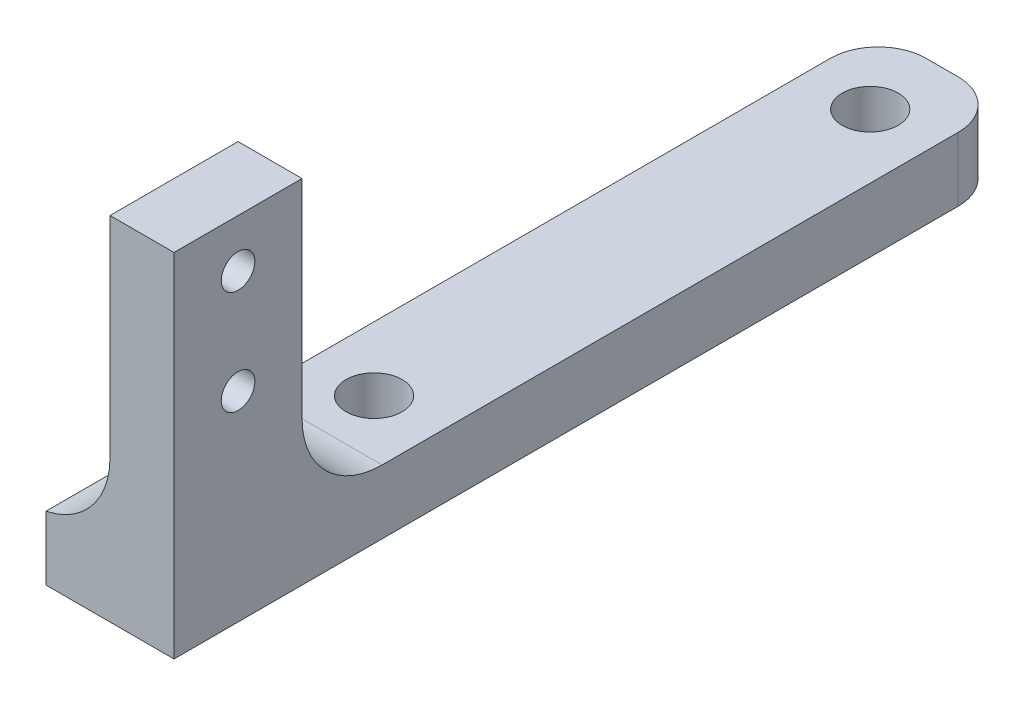
SolidWorks part; units mm, degrees
ref_plane "Front Plane" through (0, 0, 0) normal (0, 0, 1) x (1, 0, 0)
ref_plane "Top Plane" through (0, 0, 0) normal (0, 1, 0) x (1, 0, 0)
ref_plane "Right Plane" through (0, 0, 0) normal (1, 0, 0) x (0, 0, -1)
sketch "Sketch1" plane through (0, 0, 0) normal (0, 1, 0) x (1, 0, 0)
  line L2 (0, 0) -> (0, 31)
  line L3 (4, -16.5) -> (0, -16.5)
  line L10 (4, -4) -> (0, -4)
  line L11 (4, -4) -> (4, -16.5)
  line L12 (4, -16.5) -> (0, -16.5)
  line L13 (0, -4) -> (0, -16.5)
  line L14 (4, -16.5) -> (4, -8.5)
  line L15 (4, -8.5) -> (0, -8.5)
  line L16 (0, -16.5) -> (0, -8.5)
  line L17 (4, -16.5) -> (-4, -16.5)
  line L18 (4, -16.5) -> (4, 35.5)
  line L19 (4, 35.5) -> (-4, 35.5)
  line L20 (-4, -16.5) -> (-4, 35.5)
  circle A0 centre (0, 0) radius 1.75
  circle A2 centre (0, 31) radius 1.75
  dimension "D2" = 3.5
  dimension "D10" = 3.5
  dimension "D3" = 8
  dimension "D4" = 0
  dimension "D5" = 4
  dimension "D6" = 4
  dimension "D7" = 12.5
  dimension "D8" = 31
  dimension "D9" = 52
  dimension "D11" = 8
  dimension "D12" = 16.5
extrude "Boss-Extrude1" add sketch "Sketch1" along normal blind 4 contours A0 | L15 L11 L13 | L11 L15 L13 L3 region at (2, 0, 12.5) region at (-0.2884, 0, -12.0149) region at (2, 0, 6.25)
extrude "Boss-Extrude2" add sketch "Sketch1<3>" along normal blind 22 contours L11 L15 L13 L3 region at (2, 0, 12.5)
sketch "Sketch1<3>" plane through (0, 0, 0) normal (0, 1, 0) x (1, 0, 0) same geometry as "Sketch1"
sketch "Sketch3" plane through (0, 0, 0) normal (-1, 0, 0) x (0, 0, 1)
  line L0 (12.5, 22) -> (12.5, 4) construction
  line L1 (8.5, 22) -> (16.5, 22) construction
  line L2 (16.5, 4) -> (8.5, 4) construction
  circle A0 centre (12.5, 19) radius 1.05
  circle A1 centre (12.5, 12.5) radius 1.05
  dimension "D1" = 2.1
  dimension "D2" = 2.1
  dimension "D3" = 6.5
  dimension "D4" = 3
extrude "Cut-Extrude2" cut sketch "Sketch3" against normal blind 15
fillet "Fillet1" radius 5 2 edges at (0, 4, 12.5) (2, 4, 8.5)
fillet "Fillet2" radius 3 2 edges at (4, 2, -35.5) (-4, 2, -35.5)
